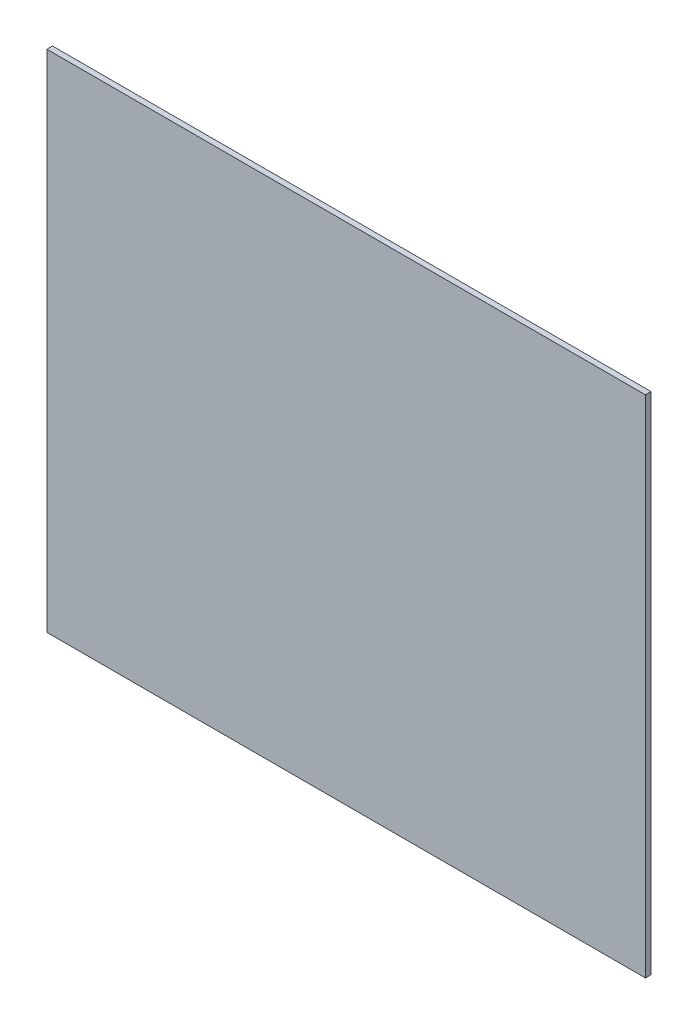
SolidWorks part; units mm, degrees
ref_plane "前视基准面" through (0, 0, 0) normal (0, 0, 1) x (1, 0, 0)
ref_plane "上视基准面" through (0, 0, 0) normal (0, 1, 0) x (1, 0, 0)
ref_plane "右视基准面" through (0, 0, 0) normal (1, 0, 0) x (0, 0, -1)
sketch "Sketch1" plane through (0, 0, 0) normal (0, 0, 1) x (1, 0, 0)
  line L1 (-160, -135) -> (160, -135)
  line L2 (-160, -135) -> (-160, 135)
  line L3 (-160, 135) -> (160, 135)
  line L4 (160, -135) -> (160, 135)
  line L5 (-160, -135) -> (160, 135) construction
  line L6 (-160, 135) -> (160, -135) construction
  point P0 (0, 0)
  dimension "D1" = 320
  dimension "D2" = 270
extrude "Boss-Extrude1" add sketch "Sketch1" along normal blind 3
